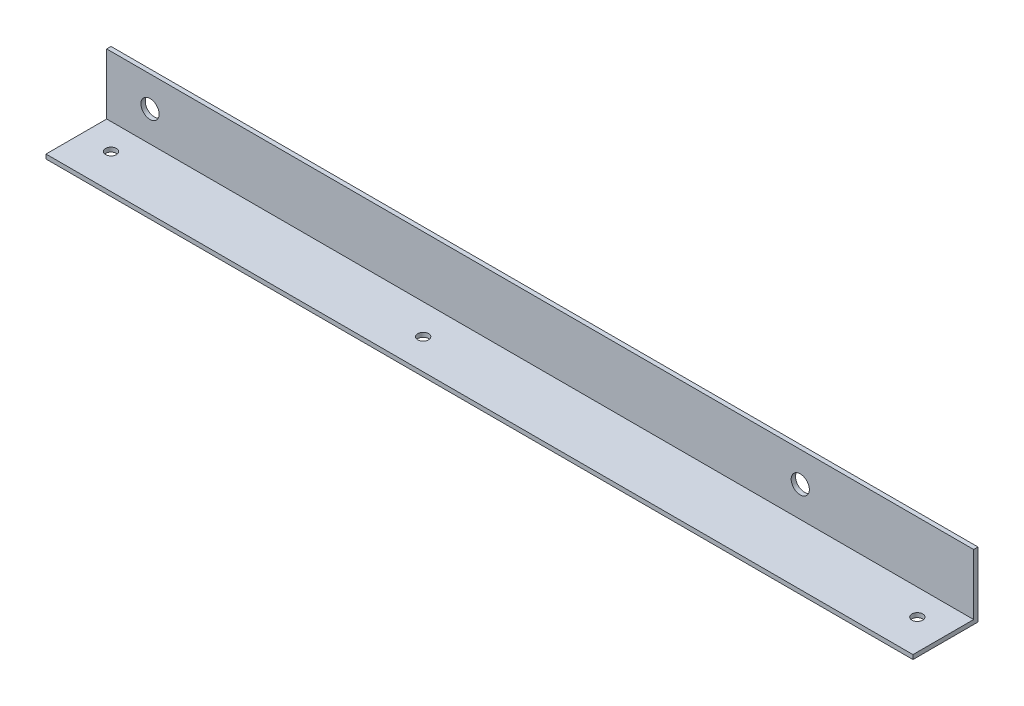
SolidWorks part; units mm, degrees
ref_plane "正面" through (0, 0, 0) normal (0, 0, 1) x (1, 0, 0)
ref_plane "平面" through (0, 0, 0) normal (0, 1, 0) x (1, 0, 0)
ref_plane "右側面" through (0, 0, 0) normal (1, 0, 0) x (0, 0, -1)
sketch "ｽｹｯﾁ1" plane through (0, 0, 0) normal (0, 0, 1) x (1, 0, 0)
  line L1 (0, 0) -> (200, 0)
  line L2 (0, 0) -> (0, 15)
  line L3 (0, 15) -> (200, 15)
  line L4 (200, 0) -> (200, 15)
  dimension "D1" = 200
  dimension "D2" = 15
extrude "ﾎﾞｽ - 押し出し1" add sketch "ｽｹｯﾁ1" along normal blind 1
sketch "ｽｹｯﾁ2" plane through (0, 0, 1) normal (0, 0, 1) x (1, 0, 0)
  line L1 (0, 0) -> (200, 0)
  line L2 (0, 0) -> (0, 1)
  line L3 (0, 1) -> (200, 1)
  line L4 (200, 0) -> (200, 1)
  dimension "D1" = 200
  dimension "D2" = 1
extrude "ﾎﾞｽ - 押し出し2" add sketch "ｽｹｯﾁ2" along normal blind 14
hole_wizard "M5x0.8 ねじ穴1" positions "ｽｹｯﾁ3" profile "ｽｹｯﾁ4" tap size "M5x0.8" standard "JIS" end condition through all
sketch "ｽｹｯﾁ3" plane through (0, 0, 0) normal (0, 0, -1) x (-1, 0, 0)
  line L0 (0, 15) -> (0, 0) construction
  line L1 (-200, 15) -> (0, 15) construction
  point P0 (-10, 8)
  point P2 (-160, 8)
  dimension "D1" = 10
  dimension "D2" = 7
  dimension "D3" = 7
  dimension "D4" = 150
sketch "ｽｹｯﾁ4" plane through (10, 8, 0) normal (1, 0, 0) x (0, 1, 0)
  line L0 (0, 0) -> (0, 15)
  line L1 (0, 15) -> (2.1, 15)
  line L2 (2.1, 15) -> (2.1, 0)
  line L5 (2.1, 0) -> (0, 0)
  line L11 (0, -6.35) -> (0, 107.95) construction
  dimension "次ｻｰﾌｪｽまでのねじ下穴ﾄﾞﾘﾙ直径" = 4.2
  dimension "次ｻｰﾌｪｽまでのねじ下穴ﾄﾞﾘﾙの深さ" = 15
cosmetic thread "穴のねじ山1" parameters "D2"=5
cosmetic thread "穴のねじ山2" parameters "D2"=5
hole_wizard "M3x0.5 ねじ穴1" positions "ｽｹｯﾁ5" profile "ｽｹｯﾁ6" tap size "M3x0.5" standard "JIS" end condition through all
sketch "ｽｹｯﾁ5" plane through (0, 0, 0) normal (0, -1, 0) x (-1, 0, 0)
  line L0 (-200, -15) -> (-200, 0) construction
  line L1 (-8.25, 0) -> (8.25, 0) construction
  point P0 (-193, -7)
  dimension "D1" = 7
  dimension "D2" = 7
sketch "ｽｹｯﾁ6" plane through (193, 0, 7) normal (1, 0, 0) x (0, 0, -1)
  line L0 (0, 0) -> (0, 15)
  line L1 (0, 15) -> (1.25, 15)
  line L2 (1.25, 15) -> (1.25, 0)
  line L5 (1.25, 0) -> (0, 0)
  line L11 (0, -6.35) -> (0, 107.95) construction
  dimension "次ｻｰﾌｪｽまでのねじ下穴ﾄﾞﾘﾙ直径" = 2.5
  dimension "次ｻｰﾌｪｽまでのねじ下穴ﾄﾞﾘﾙの深さ" = 15
cosmetic thread "穴のねじ山3" parameters "D2"=3
hole_wizard "M3x0.5 ねじ穴2" positions "ｽｹｯﾁ7" profile "ｽｹｯﾁ8" tap size "M3x0.5" standard "JIS" end condition through all
sketch "ｽｹｯﾁ7" plane through (0, 1, 0) normal (0, 1, 0) x (1, 0, 0)
  line L0 (200, -15) -> (0, -15) construction
  line L2 (200, -15) -> (200, -1) construction
  point P0 (80, -8)
  dimension "D1" = 7
  dimension "D2" = 120
sketch "ｽｹｯﾁ8" plane through (80, 1, 8) normal (1, 0, 0) x (0, 0, 1)
  line L0 (0, 0) -> (0, 1)
  line L1 (0, 1) -> (1.25, 1)
  line L2 (1.25, 1) -> (1.25, 0)
  line L5 (1.25, 0) -> (0, 0)
  line L11 (0, -6.35) -> (0, 107.95) construction
  dimension "次ｻｰﾌｪｽまでのねじ下穴ﾄﾞﾘﾙ直径" = 2.5
  dimension "次ｻｰﾌｪｽまでのねじ下穴ﾄﾞﾘﾙの深さ" = 1
cosmetic thread "穴のねじ山4" parameters "D2"=3
ref_plane "平面1" through (100, 0, 0) normal (1, 0, 0) x (0, 0, -1)
mirror "ﾐﾗｰ2" about plane through (100, 0, 0) normal (1, 0, 0) of "M3x0.5 ねじ穴1"
